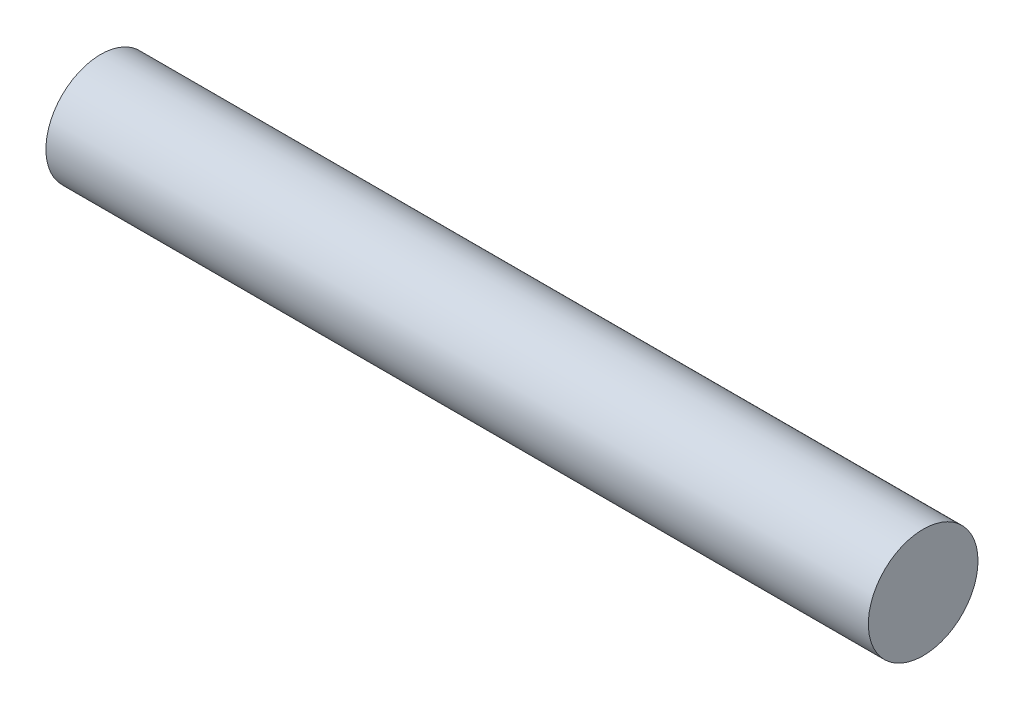
SolidWorks part; units mm, degrees
ref_plane "Front Plane" through (0, 0, 0) normal (0, 0, 1) x (1, 0, 0)
ref_plane "Top Plane" through (0, 0, 0) normal (0, 1, 0) x (1, 0, 0)
ref_plane "Right Plane" through (0, 0, 0) normal (1, 0, 0) x (0, 0, -1)
ref_plane "Top Plane X" through (-624, 0, 0) normal (1, 0, 0) x (0, 0, -1)
sketch "Pin Top Sketch" plane through (-624, 0, 0) normal (1, 0, 0) x (0, 0, -1)
  circle A0 centre (0, 117.3) radius 2
extrude "Pin Body" add sketch "Pin Top Sketch" along normal blind 30
ref_axis "Engine Axis" through (-592.5, 0, 0) along (-1, 0, 0)
